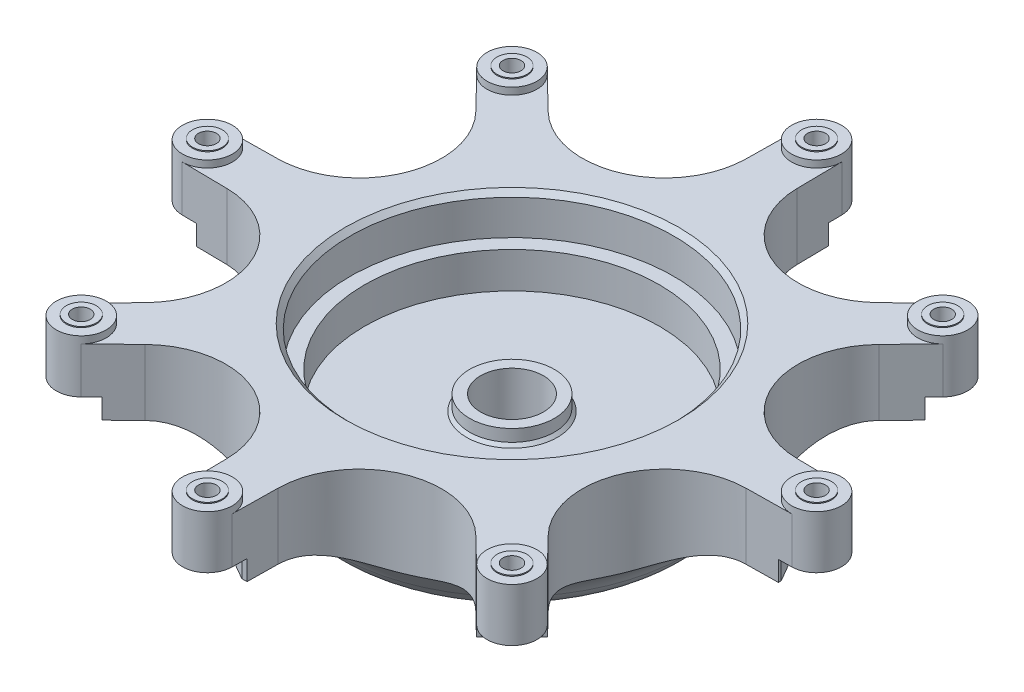
SolidWorks part; units mm, degrees
other "标注1"
sketch "草图44" plane through (33, -2.35, 33) normal (0.2303, -0.0739, 0.9703) x (-0.9702, 0.0597, 0.2348)
material "1060 合金"
ref_plane "前视基准面" through (0, 0, 0) normal (0, 0, 1) x (1, 0, 0)
ref_plane "上视基准面" through (0, 0, 0) normal (0, 1, 0) x (1, 0, 0)
ref_plane "右视基准面" through (0, 0, 0) normal (1, 0, 0) x (0, 0, -1)
sketch "草图1" plane through (0, 0, 0) normal (0, 1, 0) x (1, 0, 0)
  line L0 (-50.0728, 0) -> (48.1753, 0) construction
  line L1 (0, 42.3247) -> (0, -44.3276) construction
  line L2 (0, 0) -> (-16.3838, 39.5541) construction
  line L3 (2.4998, 30.534) -> (2.5616, 25.9875)
  line L4 (-2.4998, 30.534) -> (-2.5616, 25.9875)
  line L5 (-19.8232, 23.3584) -> (-16.5646, 20.1872)
  line L6 (19.8232, 23.3584) -> (16.5646, 20.1872)
  line L7 (23.3584, 19.8232) -> (20.1872, 16.5646)
  line L8 (30.534, 2.4998) -> (25.9875, 2.5616)
  line L9 (30.534, -2.4998) -> (25.9875, -2.5616)
  line L10 (23.3584, -19.8232) -> (20.1872, -16.5646)
  line L11 (19.8232, -23.3584) -> (16.5646, -20.1872)
  line L12 (2.4998, -30.534) -> (2.5616, -25.9875)
  line L13 (-2.4998, -30.534) -> (-2.5616, -25.9875)
  line L14 (-19.8232, -23.3584) -> (-16.5646, -20.1872)
  line L15 (-23.3584, -19.8232) -> (-20.1872, -16.5646)
  line L16 (-30.534, -2.4998) -> (-25.9875, -2.5616)
  line L17 (-30.534, 2.4998) -> (-25.9875, 2.5616)
  line L18 (-23.3584, 19.8232) -> (-20.1872, 16.5646)
  circle A0 centre (0, 0) radius 33 construction
  circle A1 centre (0, 0) radius 20 construction
  arc A2 (2.4998, 30.534) -> (-2.4998, 30.534) centre (0, 30.5) ccw
  arc A3 (-16.5646, 20.1872) -> (-2.5616, 25.9875) centre (-10.8108, 26.0996) ccw
  arc A4 (23.3584, 19.8232) -> (19.8232, 23.3584) centre (21.5668, 21.5668) ccw
  arc A5 (30.534, -2.4998) -> (30.534, 2.4998) centre (30.5, 0) ccw
  arc A6 (19.8232, -23.3584) -> (23.3584, -19.8232) centre (21.5668, -21.5668) ccw
  arc A7 (-2.4998, -30.534) -> (2.4998, -30.534) centre (0, -30.5) ccw
  arc A8 (-23.3584, -19.8232) -> (-19.8232, -23.3584) centre (-21.5668, -21.5668) ccw
  arc A9 (-30.534, 2.4998) -> (-30.534, -2.4998) centre (-30.5, 0) ccw
  arc A10 (-19.8232, 23.3584) -> (-23.3584, 19.8232) centre (-21.5668, 21.5668) ccw
  arc A11 (2.5616, 25.9875) -> (16.5646, 20.1872) centre (10.8108, 26.0996) ccw
  arc A12 (20.1872, 16.5646) -> (25.9875, 2.5616) centre (26.0996, 10.8108) ccw
  arc A13 (25.9875, -2.5616) -> (20.1872, -16.5646) centre (26.0996, -10.8108) ccw
  arc A14 (16.5646, -20.1872) -> (2.5616, -25.9875) centre (10.8108, -26.0996) ccw
  arc A15 (-2.5616, -25.9875) -> (-16.5646, -20.1872) centre (-10.8108, -26.0996) ccw
  arc A16 (-20.1872, -16.5646) -> (-25.9875, -2.5616) centre (-26.0996, -10.8108) ccw
  arc A17 (-25.9875, 2.5616) -> (-20.1872, 16.5646) centre (-26.0996, 10.8108) ccw
  point P28 (0, 0)
  point P68 (0, 0)
  dimension "D1" = 66
  dimension "D2" = 40
  dimension "D3" = 5
  dimension "D4" = 16.5
  dimension "D6" = 22.5
  dimension "D5" = 8
  dimension "D7" = 8
extrude "凸台-拉伸1" add sketch "草图1" along normal blind 13
sketch "草图2" plane through (0, 13, 0) normal (0, 1, 0) x (1, 0, 0)
  circle A0 centre (0, 0) radius 16.2
  dimension "D1" = 32.4
extrude "切除-拉伸1" cut sketch "草图2" against normal blind 10
sketch "草图4" plane through (0, 3, 0) normal (0, 1, 0) x (1, 0, 0)
  line L0 (5.227, 0) -> (-5.7752, 0) construction
  line L1 (0, 6.5094) -> (0, -4.9489) construction
  line L2 (-0.6247, 2.9342) -> (2.5165, 1.6331)
  line L3 (7.6537, 18.4776) -> (-5.316, -12.8339) construction
  arc A0 (-0.6247, 2.9342) -> (2.5165, 1.6331) centre (0, 0) ccw
  arc A1 (2.5616, 25.9875) -> (16.5646, 20.1872) centre (10.8108, 26.0996) ccw construction
  dimension "D1" = 6
  dimension "D2" = 3.4
extrude "切除-拉伸3" cut sketch "草图4" against normal blind 4
sketch "草图5" plane through (0, 3, 0) normal (0, 1, 0) x (1, 0, 0)
  line L0 (2.5165, 1.6331) -> (-0.6247, 2.9342) construction
  line L1 (2.5165, 1.6331) -> (-0.6247, 2.9342)
  line L2 (9.4419, -3.9109) -> (-11.0731, 4.5866) construction
  line L4 (-8.8639, -13.5599) -> (-4.7601, -3.6526)
  line L8 (10.8108, 26.0996) -> (-10.8108, -26.0996) construction
  line L9 (3.3206, 15.856) -> (-0.7832, 5.9487)
  line L10 (8.8639, 13.5599) -> (4.7601, 3.6526)
  line L11 (-3.3206, -15.856) -> (0.7832, -5.9487)
  arc A1 (-0.6247, 2.9342) -> (2.5165, 1.6331) centre (0, 0) ccw construction
  arc A2 (-0.6247, 2.9342) -> (2.5165, 1.6331) centre (0, 0) ccw
  arc A9 (-0.7832, 5.9487) -> (-4.7601, -3.6526) centre (0, 0) ccw
  circle A10 centre (0, 0) radius 16.2 construction
  arc A11 (-8.8639, -13.5599) -> (-3.3206, -15.856) centre (0, 0) ccw
  arc A12 (8.8639, 13.5599) -> (3.3206, 15.856) centre (0, 0) ccw
  arc A13 (0.7832, -5.9487) -> (4.7601, 3.6526) centre (0, 0) ccw
  dimension "D1" = 12
  dimension "D2" = 3
extrude "凸台-拉伸2" add sketch "草图5" along normal blind 3
sketch "草图6" plane through (0.9459, 0, -2.2837) normal (-0.3827, 0, 0.9239) x (0.9239, 0, 0.3827)
  line L0 (1.7, 0) -> (-1.7, 0) construction
  line L1 (0, -6.3083) -> (0, 25.3253) construction
  circle A0 centre (0, 3) radius 1.55
  dimension "D1" = 3.1
  dimension "D2" = 3
extrude "切除-拉伸4" cut sketch "草图6" along normal through all
sketch "草图8" plane through (0.9459, 0, -2.2837) normal (-0.3827, 0, 0.9239) x (0.9239, 0, 0.3827)
  circle A0 centre (0, 3) radius 1.55 construction
  circle A1 centre (0, 3) radius 1.55
hole_wizard "M3 螺纹孔1" positions "3D草图2" profile "草图9" tap size "M3" standard "GB" end condition through all
sketch3d "3D草图2"
  point P0 (0.9459, 3, -2.2837)
sketch "草图9" plane through (0.9459, 3, -2.2837) normal (0, 1, 0) x (0.9239, 0, 0.3827)
  line L0 (0, 0) -> (0, 40.6447)
  line L1 (0, 40.6447) -> (1.25, 40.6447)
  line L2 (1.25, 40.6447) -> (1.25, 0)
  line L5 (1.25, 0) -> (0, 0)
  line L11 (0, -6.35) -> (0, 107.95) construction
  dimension "通孔螺纹孔钻头直径" = 2.5
  dimension "通孔螺纹孔钻头深度" = 40.6447
cosmetic thread "孔螺蚊线1" parameters "D2"=3
ref_plane "基准面1" through (-3.6463, 0, 8.8029) normal (-0.3827, 0, 0.9239) x (0.9239, 0, 0.3827)
sketch "草图10" plane through (-3.6463, 0, 8.8029) normal (-0.3827, 0, 0.9239) x (0.9239, 0, 0.3827)
  circle A0 centre (0, 3) radius 1.55 construction
  circle A1 centre (0, 3) radius 1.55 construction
  circle A2 centre (0, 3) radius 2.9
  dimension "D1" = 5.8
extrude "切除-拉伸6" cut sketch "草图10" along normal through all
sketch "草图16" plane through (0, 0, 0) normal (0, -1, 0) x (1, 0, 0)
  circle A0 centre (0, 0) radius 3
  dimension "D1" = 6
extrude "切除-拉伸7" cut sketch "草图16" against normal blind 10
sketch "草图22" plane through (0, 3, 0) normal (0, 1, 0) x (1, 0, 0)
  line L4 (-0.7832, 5.9487) -> (3.3206, 15.856)
  line L7 (-8.8639, -13.5599) -> (-4.7601, -3.6526)
  line L8 (-0.7832, 5.9487) -> (3.3206, 15.856)
  line L11 (-8.8639, -13.5599) -> (-4.7601, -3.6526)
  line L12 (0.7832, -5.9487) -> (-3.3206, -15.856)
  line L13 (8.8639, 13.5599) -> (4.7601, 3.6526)
  line L16 (0.7832, -5.9487) -> (-3.3206, -15.856)
  line L17 (8.8639, 13.5599) -> (4.7601, 3.6526)
  arc A2 (-0.7832, 5.9487) -> (-4.7601, -3.6526) centre (0, 0) ccw
  arc A3 (3.3206, 15.856) -> (-8.8639, -13.5599) centre (0, 0) ccw
  arc A4 (-0.7832, 5.9487) -> (-4.7601, -3.6526) centre (0, 0) ccw
  arc A5 (3.3206, 15.856) -> (-8.8639, -13.5599) centre (0, 0) ccw
  arc A6 (0.7832, -5.9487) -> (4.7601, 3.6526) centre (0, 0) ccw
  arc A7 (-3.3206, -15.856) -> (8.8639, 13.5599) centre (0, 0) ccw
  arc A8 (0.7832, -5.9487) -> (4.7601, 3.6526) centre (0, 0) ccw
  arc A9 (-3.3206, -15.856) -> (8.8639, 13.5599) centre (0, 0) ccw
  dimension "D1" = 0
  dimension "D2" = 0
extrude "凸台-拉伸7" add sketch "草图22" along normal up to surface (3 mm away) up to face at (0, 6, 3)
extrude "切除-拉伸9" cut sketch "草图8" against normal blind 22 contours A1
sketch "草图24" plane through (0, 6, 0) normal (0, 1, 0) x (1, 0, 0)
  circle A0 centre (0, 0) radius 3 construction
  circle A1 centre (0, 0) radius 3
  circle A2 centre (0, 0) radius 4.25
  dimension "D1" = 8.5
extrude "凸台-拉伸9" add sketch "草图24" along normal blind 1.5
sketch "草图26" plane through (0, 0, 0) normal (0, -1, 0) x (1, 0, 0)
  circle A0 centre (0, 0) radius 3 construction
  circle A1 centre (0, 0) radius 3
  circle A2 centre (0, 0) radius 6
  dimension "D1" = 12
extrude "凸台-拉伸11" add sketch "草图26" along normal blind 1.5
sketch "草图27" plane through (0, -1.5, 0) normal (0, -1, 0) x (1, 0, 0)
  circle A0 centre (0, 0) radius 3.15
  dimension "D1" = 6.3
extrude "切除-拉伸10" cut sketch "草图27" against normal blind 17.4
sketch "草图28" plane through (0, 6, 0) normal (0, 1, 0) x (1, 0, 0)
  circle A0 centre (0, 0) radius 14.75
  circle A1 centre (0, 0) radius 16.2 construction
  circle A2 centre (0, 0) radius 16.2
  dimension "D1" = 29.5
extrude "凸台-拉伸12" add sketch "草图28" along normal blind 3.6
sketch "草图30" plane through (0, 13, 0) normal (0, 1, 0) x (1, 0, 0)
  line L16 (-25.9875, 2.5616) -> (-30.534, 2.4998)
  line L17 (-30.534, -2.4998) -> (-25.9875, -2.5616)
  line L18 (-20.1872, -16.5646) -> (-23.3584, -19.8232)
  line L19 (-19.8232, -23.3584) -> (-16.5646, -20.1872)
  line L20 (-2.5616, -25.9875) -> (-2.4998, -30.534)
  line L21 (2.4998, -30.534) -> (2.5616, -25.9875)
  line L22 (16.5646, -20.1872) -> (19.8232, -23.3584)
  line L23 (23.3584, -19.8232) -> (20.1872, -16.5646)
  line L24 (25.9875, -2.5616) -> (30.534, -2.4998)
  line L25 (30.534, 2.4998) -> (25.9875, 2.5616)
  line L26 (20.1872, 16.5646) -> (23.3584, 19.8232)
  line L27 (19.8232, 23.3584) -> (16.5646, 20.1872)
  line L28 (2.5616, 25.9875) -> (2.4998, 30.534)
  line L29 (-2.4998, 30.534) -> (-2.5616, 25.9875)
  line L30 (-16.5646, 20.1872) -> (-19.8232, 23.3584)
  line L31 (-23.3584, 19.8232) -> (-20.1872, 16.5646)
  line L32 (-25.9875, 2.5616) -> (-30.534, 2.4998)
  line L33 (-30.534, -2.4998) -> (-25.9875, -2.5616)
  line L34 (-20.1872, -16.5646) -> (-23.3584, -19.8232)
  line L35 (-19.8232, -23.3584) -> (-16.5646, -20.1872)
  line L36 (-2.5616, -25.9875) -> (-2.4998, -30.534)
  line L37 (2.4998, -30.534) -> (2.5616, -25.9875)
  line L38 (16.5646, -20.1872) -> (19.8232, -23.3584)
  line L39 (23.3584, -19.8232) -> (20.1872, -16.5646)
  line L40 (25.9875, -2.5616) -> (30.534, -2.4998)
  line L41 (30.534, 2.4998) -> (25.9875, 2.5616)
  line L42 (20.1872, 16.5646) -> (23.3584, 19.8232)
  line L43 (19.8232, 23.3584) -> (16.5646, 20.1872)
  line L44 (2.5616, 25.9875) -> (2.4998, 30.534)
  line L45 (-2.4998, 30.534) -> (-2.5616, 25.9875)
  line L46 (-16.5646, 20.1872) -> (-19.8232, 23.3584)
  line L47 (-23.3584, 19.8232) -> (-20.1872, 16.5646)
  arc A16 (-30.534, 2.4998) -> (-30.534, -2.4998) centre (-30.5, 0) ccw
  arc A17 (-20.1872, -16.5646) -> (-25.9875, -2.5616) centre (-26.0996, -10.8108) ccw
  arc A18 (-23.3584, -19.8232) -> (-19.8232, -23.3584) centre (-21.5668, -21.5668) ccw
  arc A19 (-2.5616, -25.9875) -> (-16.5646, -20.1872) centre (-10.8108, -26.0996) ccw
  arc A20 (-2.4998, -30.534) -> (2.4998, -30.534) centre (0, -30.5) ccw
  arc A21 (16.5646, -20.1872) -> (2.5616, -25.9875) centre (10.8108, -26.0996) ccw
  arc A22 (19.8232, -23.3584) -> (23.3584, -19.8232) centre (21.5668, -21.5668) ccw
  arc A23 (25.9875, -2.5616) -> (20.1872, -16.5646) centre (26.0996, -10.8108) ccw
  arc A24 (30.534, -2.4998) -> (30.534, 2.4998) centre (30.5, 0) ccw
  arc A25 (20.1872, 16.5646) -> (25.9875, 2.5616) centre (26.0996, 10.8108) ccw
  arc A26 (23.3584, 19.8232) -> (19.8232, 23.3584) centre (21.5668, 21.5668) ccw
  arc A27 (2.5616, 25.9875) -> (16.5646, 20.1872) centre (10.8108, 26.0996) ccw
  arc A28 (2.4998, 30.534) -> (-2.4998, 30.534) centre (0, 30.5) ccw
  arc A29 (-16.5646, 20.1872) -> (-2.5616, 25.9875) centre (-10.8108, 26.0996) ccw
  arc A30 (-19.8232, 23.3584) -> (-23.3584, 19.8232) centre (-21.5668, 21.5668) ccw
  arc A31 (-25.9875, 2.5616) -> (-20.1872, 16.5646) centre (-26.0996, 10.8108) ccw
  arc A32 (-30.534, 2.4998) -> (-30.534, -2.4998) centre (-30.5, 0) ccw
  arc A33 (-20.1872, -16.5646) -> (-25.9875, -2.5616) centre (-26.0996, -10.8108) ccw
  arc A34 (-23.3584, -19.8232) -> (-19.8232, -23.3584) centre (-21.5668, -21.5668) ccw
  arc A35 (-2.5616, -25.9875) -> (-16.5646, -20.1872) centre (-10.8108, -26.0996) ccw
  arc A36 (-2.4998, -30.534) -> (2.4998, -30.534) centre (0, -30.5) ccw
  arc A37 (16.5646, -20.1872) -> (2.5616, -25.9875) centre (10.8108, -26.0996) ccw
  arc A38 (19.8232, -23.3584) -> (23.3584, -19.8232) centre (21.5668, -21.5668) ccw
  arc A39 (25.9875, -2.5616) -> (20.1872, -16.5646) centre (26.0996, -10.8108) ccw
  arc A40 (30.534, -2.4998) -> (30.534, 2.4998) centre (30.5, 0) ccw
  arc A41 (20.1872, 16.5646) -> (25.9875, 2.5616) centre (26.0996, 10.8108) ccw
  arc A42 (23.3584, 19.8232) -> (19.8232, 23.3584) centre (21.5668, 21.5668) ccw
  arc A43 (2.5616, 25.9875) -> (16.5646, 20.1872) centre (10.8108, 26.0996) ccw
  arc A44 (2.4998, 30.534) -> (-2.4998, 30.534) centre (0, 30.5) ccw
  arc A45 (-16.5646, 20.1872) -> (-2.5616, 25.9875) centre (-10.8108, 26.0996) ccw
  arc A46 (-19.8232, 23.3584) -> (-23.3584, 19.8232) centre (-21.5668, 21.5668) ccw
  arc A47 (-25.9875, 2.5616) -> (-20.1872, 16.5646) centre (-26.0996, 10.8108) ccw
  dimension "D1" = 0
extrude "切除-拉伸12" cut sketch "草图30" against normal blind 0.4
chamfer "倒角6" distance 0.3 angle 45 1 edges at (0, 6, 4.25)
sketch "草图32" plane through (0, 0, 0) normal (0, -1, 0) x (1, 0, 0)
  line L0 (-18.4776, 7.6537) -> (-7.6537, -18.4776) construction
  arc A0 (-25.9875, 2.5616) -> (-20.1872, 16.5646) centre (-26.0996, 10.8108) ccw construction
  arc A1 (-2.5616, -25.9875) -> (-16.5646, -20.1872) centre (-10.8108, -26.0996) ccw construction
  text T0 "外径62mm"
wrap "包覆1" [suppressed] sketch "草图32" source sketch "草图32" thickness 0.5 parameters "D1"=0.5
sketch "草图33" plane through (0, 0, 0) normal (0, -1, 0) x (1, 0, 0)
  line L0 (-18.4776, 7.6537) -> (-7.6537, -18.4776) construction
  arc A0 (-25.9875, 2.5616) -> (-20.1872, 16.5646) centre (-26.0996, 10.8108) ccw construction
  arc A1 (-2.5616, -25.9875) -> (-16.5646, -20.1872) centre (-10.8108, -26.0996) ccw construction
  text T0 "外径64mm"
wrap "包覆2" [suppressed] sketch "草图33" source sketch "草图33" thickness 0.5 parameters "D1"=0.5
sketch "草图34" plane through (0, 0, 0) normal (0, -1, 0) x (1, 0, 0)
  circle A0 centre (0, 0) radius 16.5
  circle A1 centre (0, 0) radius 33
  arc A2 (19.8232, -23.3584) -> (23.3584, -19.8232) centre (21.5668, -21.5668) ccw construction
  dimension "D1" = 33
extrude "切除-拉伸13" cut sketch "草图34" against normal blind 7
chamfer "倒角7" [suppressed] distance 2 angle 45
sketch "草图35" plane through (0, 0, 0) normal (0, -1, 0) x (1, 0, 0)
  circle A1 centre (0, 0) radius 6.5
  dimension "D1" = 13
extrude "切除-拉伸14" [suppressed] cut sketch "草图35" along normal blind 3
fillet "圆角2" [suppressed] radius 2.5
chamfer "倒角8" [suppressed] distance 2 angle 45
sketch "草图37" plane through (0, 12.6, 0) normal (0, 1, 0) x (1, 0, 0)
  line L16 (-25.9875, 2.5616) -> (-30.534, 2.4998)
  line L17 (-30.534, -2.4998) -> (-25.9875, -2.5616)
  line L18 (-20.1872, -16.5646) -> (-23.3584, -19.8232)
  line L19 (-19.8232, -23.3584) -> (-16.5646, -20.1872)
  line L20 (-2.5616, -25.9875) -> (-2.4998, -30.534)
  line L21 (2.4998, -30.534) -> (2.5616, -25.9875)
  line L22 (16.5646, -20.1872) -> (19.8232, -23.3584)
  line L23 (23.3584, -19.8232) -> (20.1872, -16.5646)
  line L24 (25.9875, -2.5616) -> (30.534, -2.4998)
  line L25 (30.534, 2.4998) -> (25.9875, 2.5616)
  line L26 (20.1872, 16.5646) -> (23.3584, 19.8232)
  line L27 (19.8232, 23.3584) -> (16.5646, 20.1872)
  line L28 (2.5616, 25.9875) -> (2.4998, 30.534)
  line L29 (-2.4998, 30.534) -> (-2.5616, 25.9875)
  line L30 (-16.5646, 20.1872) -> (-19.8232, 23.3584)
  line L31 (-23.3584, 19.8232) -> (-20.1872, 16.5646)
  line L32 (-25.9875, 2.5616) -> (-30.534, 2.4998)
  line L33 (-30.534, -2.4998) -> (-25.9875, -2.5616)
  line L34 (-20.1872, -16.5646) -> (-23.3584, -19.8232)
  line L35 (-19.8232, -23.3584) -> (-16.5646, -20.1872)
  line L36 (-2.5616, -25.9875) -> (-2.4998, -30.534)
  line L37 (2.4998, -30.534) -> (2.5616, -25.9875)
  line L38 (16.5646, -20.1872) -> (19.8232, -23.3584)
  line L39 (23.3584, -19.8232) -> (20.1872, -16.5646)
  line L40 (25.9875, -2.5616) -> (30.534, -2.4998)
  line L41 (30.534, 2.4998) -> (25.9875, 2.5616)
  line L42 (20.1872, 16.5646) -> (23.3584, 19.8232)
  line L43 (19.8232, 23.3584) -> (16.5646, 20.1872)
  line L44 (2.5616, 25.9875) -> (2.4998, 30.534)
  line L45 (-2.4998, 30.534) -> (-2.5616, 25.9875)
  line L46 (-16.5646, 20.1872) -> (-19.8232, 23.3584)
  line L47 (-23.3584, 19.8232) -> (-20.1872, 16.5646)
  circle A0 centre (0, 0) radius 16.2 construction
  circle A1 centre (0, 0) radius 16.2
  arc A16 (-25.9875, 2.5616) -> (-20.1872, 16.5646) centre (-26.0996, 10.8108) ccw
  arc A17 (-30.534, 2.4998) -> (-30.534, -2.4998) centre (-30.5, 0) ccw
  arc A18 (-20.1872, -16.5646) -> (-25.9875, -2.5616) centre (-26.0996, -10.8108) ccw
  arc A19 (-30.534, 2.4998) -> (-30.534, -2.4998) centre (-30.5, 0) ccw
  arc A20 (-2.5616, -25.9875) -> (-16.5646, -20.1872) centre (-10.8108, -26.0996) ccw
  arc A21 (-23.3584, -19.8232) -> (-19.8232, -23.3584) centre (-21.5668, -21.5668) ccw
  arc A22 (16.5646, -20.1872) -> (2.5616, -25.9875) centre (10.8108, -26.0996) ccw
  arc A23 (-23.3584, -19.8232) -> (-19.8232, -23.3584) centre (-21.5668, -21.5668) ccw
  arc A24 (25.9875, -2.5616) -> (20.1872, -16.5646) centre (26.0996, -10.8108) ccw
  arc A25 (-2.4998, -30.534) -> (2.4998, -30.534) centre (0, -30.5) ccw
  arc A26 (20.1872, 16.5646) -> (25.9875, 2.5616) centre (26.0996, 10.8108) ccw
  arc A27 (-2.4998, -30.534) -> (2.4998, -30.534) centre (0, -30.5) ccw
  arc A28 (2.5616, 25.9875) -> (16.5646, 20.1872) centre (10.8108, 26.0996) ccw
  arc A29 (19.8232, -23.3584) -> (23.3584, -19.8232) centre (21.5668, -21.5668) ccw
  arc A30 (-16.5646, 20.1872) -> (-2.5616, 25.9875) centre (-10.8108, 26.0996) ccw
  arc A31 (19.8232, -23.3584) -> (23.3584, -19.8232) centre (21.5668, -21.5668) ccw
  arc A32 (-25.9875, 2.5616) -> (-20.1872, 16.5646) centre (-26.0996, 10.8108) ccw
  arc A34 (-20.1872, -16.5646) -> (-25.9875, -2.5616) centre (-26.0996, -10.8108) ccw
  arc A36 (-2.5616, -25.9875) -> (-16.5646, -20.1872) centre (-10.8108, -26.0996) ccw
  arc A38 (16.5646, -20.1872) -> (2.5616, -25.9875) centre (10.8108, -26.0996) ccw
  arc A40 (25.9875, -2.5616) -> (20.1872, -16.5646) centre (26.0996, -10.8108) ccw
  arc A42 (20.1872, 16.5646) -> (25.9875, 2.5616) centre (26.0996, 10.8108) ccw
  arc A44 (2.5616, 25.9875) -> (16.5646, 20.1872) centre (10.8108, 26.0996) ccw
  arc A46 (-16.5646, 20.1872) -> (-2.5616, 25.9875) centre (-10.8108, 26.0996) ccw
  arc A50 (30.534, -2.4998) -> (30.534, 2.4998) centre (30.5, 0) ccw
  arc A51 (30.534, -2.4998) -> (30.534, 2.4998) centre (30.5, 0) ccw
  arc A52 (23.3584, 19.8232) -> (19.8232, 23.3584) centre (21.5668, 21.5668) ccw
  arc A53 (23.3584, 19.8232) -> (19.8232, 23.3584) centre (21.5668, 21.5668) ccw
  arc A54 (2.4998, 30.534) -> (-2.4998, 30.534) centre (0, 30.5) ccw
  arc A55 (2.4998, 30.534) -> (-2.4998, 30.534) centre (0, 30.5) ccw
  arc A56 (-19.8232, 23.3584) -> (-23.3584, 19.8232) centre (-21.5668, 21.5668) ccw
  arc A57 (-19.8232, 23.3584) -> (-23.3584, 19.8232) centre (-21.5668, 21.5668) ccw
  dimension "D1" = 0
extrude "凸台-拉伸16" add sketch "草图37" along normal blind 1
fillet "圆角6" radius 10 1 edges at (0, 7, -16.5)
chamfer "倒角10" distance 0.5 angle 45 1 edges at (0, 13.6, 16.2)
sketch "草图38" plane through (0, 0, 0) normal (0, -1, 0) x (1, 0, 0)
  line L0 (16.3111, -2.4895) -> (5.4274, 15.5818) construction
  circle A1 centre (0, 0) radius 16.5 construction
  text T0 "<b>66mm</b>" font "汉仪长仿宋体" height 5
  dimension "D1" = 12
wrap "包覆3" [suppressed] sketch "草图38" source sketch "草图38" thickness 0.5 parameters "D1"=0.5
sketch "草图39" plane through (0, 0, 0) normal (0, -1, 0) x (1, 0, 0)
  line L0 (15.9602, -4.1861) -> (5.1024, 15.6913) construction
  circle A0 centre (0, 0) radius 16.5 construction
  text T0 "64mm" font "汉仪长仿宋体" height 5
  dimension "D1" = 12
wrap "包覆4" [suppressed] sketch "草图39" source sketch "草图39" thickness 0.5 parameters "D1"=0.5
sketch "草图40" plane through (0, 13.6, 0) normal (0, 1, 0) x (1, 0, 0)
  circle A0 centre (0, -30.5) radius 2.5
  arc A1 (-2.4998, -30.534) -> (2.4998, -30.534) centre (0, -30.5) ccw construction
  circle A2 centre (-21.5668, -21.5668) radius 2.5
  circle A3 centre (-30.5, 0) radius 2.5
  circle A4 centre (-21.5668, 21.5668) radius 2.5
  circle A5 centre (0, 30.5) radius 2.5
  circle A6 centre (21.5668, 21.5668) radius 2.5
  circle A7 centre (30.5, 0) radius 2.5
  circle A8 centre (21.5668, -21.5668) radius 2.5
  point P22 (0, 0)
  dimension "D1" = 8
extrude "凸台-拉伸17" add sketch "草图40" along normal blind 0.7
sketch "草图41" plane through (0, 14.3, 0) normal (0, 1, 0) x (1, 0, 0)
  circle A0 centre (0, -30.5) radius 1.5
  circle A1 centre (-21.5668, -21.5668) radius 1.5
  circle A2 centre (-30.5, 0) radius 1.5
  circle A3 centre (-21.5668, 21.5668) radius 1.5
  circle A4 centre (0, 30.5) radius 1.5
  circle A5 centre (21.5668, 21.5668) radius 1.5
  circle A6 centre (30.5, 0) radius 1.5
  circle A7 centre (21.5668, -21.5668) radius 1.5
  point P19 (0, 0)
  dimension "D1" = 3
  dimension "D2" = 8
extrude "凸台-拉伸18" add sketch "草图41" along normal blind 0.1
sketch "草图42" plane through (0, 14.4, 0) normal (0, 1, 0) x (1, 0, 0)
  circle A0 centre (0, -30.5) radius 0.9
  circle A1 centre (-21.5668, -21.5668) radius 0.9
  circle A2 centre (-30.5, 0) radius 0.9
  circle A3 centre (-21.5668, 21.5668) radius 0.9
  circle A4 centre (0, 30.5) radius 0.9
  circle A5 centre (21.5668, 21.5668) radius 0.9
  circle A6 centre (30.5, 0) radius 0.9
  circle A7 centre (21.5668, -21.5668) radius 0.9
  point P20 (0, 0)
  dimension "D1" = 1.8
  dimension "D2" = 8
extrude "切除-拉伸15" cut sketch "草图42" against normal blind 9.5
sketch "草图43" plane through (-3.6463, 0, 8.8029) normal (-0.3827, 0, 0.9239) x (0.9239, 0, 0.3827)
  circle A0 centre (0, 3) radius 1.55 construction
  circle A1 centre (0, 3) radius 1.55
  circle A2 centre (0, 3) radius 1.25
  dimension "D1" = 2.5
extrude "凸台-拉伸19" add sketch "草图43" against normal up to surface (9.5008 mm away) from offset 18 up to face at (0, 0, -16.5) offset against normal yes
chamfer "倒角11" distance 0.5 angle 45 1 edges at (0, -1.5, -6)
chamfer "倒角12" distance 0.5 angle 45 1 edges at (0, -1.5, -3.15)
sketch "草图46" plane through (0, 7, 0) normal (0, -1, 0) x (1, 0, 0)
  line L0 (-19.7296, -19.7296) -> (-22.2392, -19.0572)
  line L1 (0, -33.0981) -> (2.25, -31.799)
  line L2 (2.25, -31.799) -> (2.25, -29.201)
  line L3 (2.25, -29.201) -> (0, -27.9019)
  line L4 (0, -27.9019) -> (-2.25, -29.201)
  line L5 (-2.25, -29.201) -> (-2.25, -31.799)
  line L6 (-2.25, -31.799) -> (0, -33.0981)
  line L7 (-19.0572, -22.2392) -> (-19.7296, -19.7296)
  line L8 (-20.8943, -24.0763) -> (-19.0572, -22.2392)
  line L9 (-23.4039, -23.4039) -> (-20.8943, -24.0763)
  line L10 (-24.0763, -20.8943) -> (-23.4039, -23.4039)
  line L11 (-22.2392, -19.0572) -> (-24.0763, -20.8943)
  line L12 (-27.9019, 0) -> (-29.201, 2.25)
  line L13 (-29.201, -2.25) -> (-27.9019, 0)
  line L14 (-31.799, -2.25) -> (-29.201, -2.25)
  line L15 (-33.0981, 0) -> (-31.799, -2.25)
  line L16 (-31.799, 2.25) -> (-33.0981, 0)
  line L17 (-29.201, 2.25) -> (-31.799, 2.25)
  line L18 (-19.7296, 19.7296) -> (-19.0572, 22.2392)
  line L19 (-22.2392, 19.0572) -> (-19.7296, 19.7296)
  line L20 (-24.0763, 20.8943) -> (-22.2392, 19.0572)
  line L21 (-23.4039, 23.4039) -> (-24.0763, 20.8943)
  line L22 (-20.8943, 24.0763) -> (-23.4039, 23.4039)
  line L23 (-19.0572, 22.2392) -> (-20.8943, 24.0763)
  line L24 (0, 27.9019) -> (2.25, 29.201)
  line L25 (-2.25, 29.201) -> (0, 27.9019)
  line L26 (-2.25, 31.799) -> (-2.25, 29.201)
  line L27 (0, 33.0981) -> (-2.25, 31.799)
  line L28 (2.25, 31.799) -> (0, 33.0981)
  line L29 (2.25, 29.201) -> (2.25, 31.799)
  line L30 (19.7296, 19.7296) -> (22.2392, 19.0572)
  line L31 (19.0572, 22.2392) -> (19.7296, 19.7296)
  line L32 (20.8943, 24.0763) -> (19.0572, 22.2392)
  line L33 (23.4039, 23.4039) -> (20.8943, 24.0763)
  line L34 (24.0763, 20.8943) -> (23.4039, 23.4039)
  line L35 (22.2392, 19.0572) -> (24.0763, 20.8943)
  line L36 (27.9019, 0) -> (29.201, -2.25)
  line L37 (29.201, 2.25) -> (27.9019, 0)
  line L38 (31.799, 2.25) -> (29.201, 2.25)
  line L39 (33.0981, 0) -> (31.799, 2.25)
  line L40 (31.799, -2.25) -> (33.0981, 0)
  line L41 (29.201, -2.25) -> (31.799, -2.25)
  line L42 (19.7296, -19.7296) -> (19.0572, -22.2392)
  line L43 (22.2392, -19.0572) -> (19.7296, -19.7296)
  line L44 (24.0763, -20.8943) -> (22.2392, -19.0572)
  line L45 (23.4039, -23.4039) -> (24.0763, -20.8943)
  line L46 (20.8943, -24.0763) -> (23.4039, -23.4039)
  line L47 (19.0572, -22.2392) -> (20.8943, -24.0763)
  circle A0 centre (0, -30.5) radius 2.25 construction
  dimension "D1" = 4.5
  dimension "D2" = 8
extrude "切除-拉伸17" cut sketch "草图46" against normal blind 2
fillet "圆角10" radius 5 1 edges at (0, 0, -16.5)
sketch "草图47" plane through (0, 7, 0) normal (0, -1, 0) x (1, 0, 0)
  line L0 (-3.3702, -29.201) -> (3.1162, -29.201)
  line L1 (3.1162, -29.201) -> (3.1162, -33.3642)
  line L2 (3.1162, -33.3642) -> (-3.3702, -33.2422)
  line L3 (-3.3702, -33.2422) -> (-3.3702, -29.201)
  line L4 (-18.3725, -22.8218) -> (-21.3164, -25.7657)
  line L5 (-21.3164, -25.7657) -> (-25.8167, -21.0928)
  line L6 (-22.9591, -18.2352) -> (-18.3725, -22.8218)
  line L7 (-25.8167, -21.0928) -> (-22.9591, -18.2352)
  line L8 (-29.0566, -3.1162) -> (-33.2199, -3.1162)
  line L9 (-33.2199, -3.1162) -> (-33.0978, 3.3702)
  line L10 (-29.0566, 3.3702) -> (-29.0566, -3.1162)
  line L11 (-33.0978, 3.3702) -> (-29.0566, 3.3702)
  line L12 (-22.6775, 18.3725) -> (-25.6213, 21.3164)
  line L13 (-25.6213, 21.3164) -> (-20.9485, 25.8167)
  line L14 (-18.0909, 22.9591) -> (-22.6775, 18.3725)
  line L15 (-20.9485, 25.8167) -> (-18.0909, 22.9591)
  line L16 (-2.9719, 29.0566) -> (-2.9719, 33.2199)
  line L17 (-2.9719, 33.2199) -> (3.5145, 33.0978)
  line L18 (3.5145, 29.0566) -> (-2.9719, 29.0566)
  line L19 (3.5145, 33.0978) -> (3.5145, 29.0566)
  line L20 (18.5169, 22.6775) -> (21.4607, 25.6213)
  line L21 (21.4607, 25.6213) -> (25.961, 20.9485)
  line L22 (23.1034, 18.0909) -> (18.5169, 22.6775)
  line L23 (25.961, 20.9485) -> (23.1034, 18.0909)
  line L24 (29.201, 2.9719) -> (33.3642, 2.9719)
  line L25 (33.3642, 2.9719) -> (33.2422, -3.5145)
  line L26 (29.201, -3.5145) -> (29.201, 2.9719)
  line L27 (33.2422, -3.5145) -> (29.201, -3.5145)
  line L28 (22.8218, -18.5169) -> (25.7657, -21.4607)
  line L29 (25.7657, -21.4607) -> (21.0928, -25.961)
  line L30 (18.2352, -23.1034) -> (22.8218, -18.5169)
  line L31 (21.0928, -25.961) -> (18.2352, -23.1034)
  dimension "D1" = 8
extrude "切除-拉伸18" cut sketch "草图47" against normal blind 2
